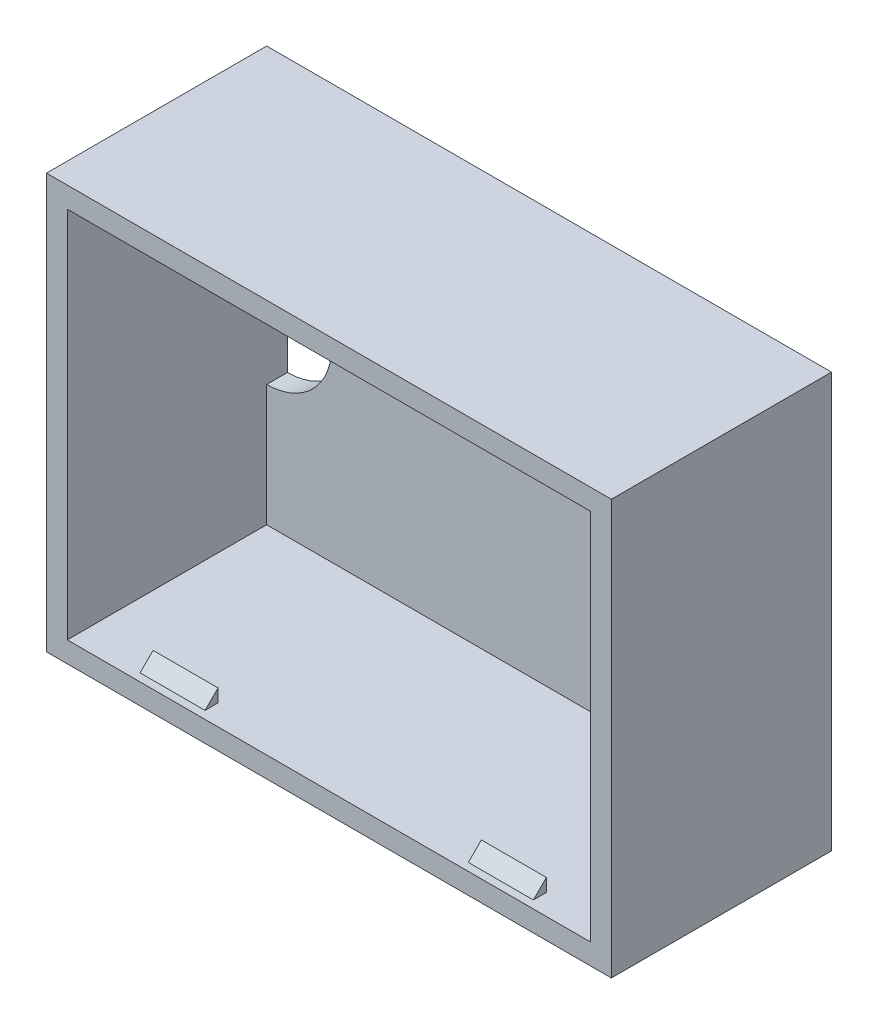
SolidWorks part; units mm, degrees
ref_plane "Front Plane" through (0, 0, 0) normal (1, 0, 0) x (0, 1, 0)
ref_plane "Top Plane" through (0, 0, 0) normal (0, 0, 1) x (0, 1, 0)
ref_plane "Right Plane" through (0, 0, 0) normal (0, 1, 0) x (-1, 0, 0)
sketch "Sketch2" plane through (0, 0, 0) normal (0, 0, 1) x (0, 1, 0)
  line L1 (-15.95, -21.73) -> (15.95, -21.73)
  line L2 (-15.95, -21.73) -> (-15.95, 21.73)
  line L3 (-15.95, 21.73) -> (15.95, 21.73)
  line L4 (15.95, -21.73) -> (15.95, 21.73)
  line L5 (-15.95, -21.73) -> (15.95, 21.73) construction
  line L6 (-15.95, 21.73) -> (15.95, -21.73) construction
  point P0 (0, 0)
  dimension "D1" = 43.46
  dimension "D2" = 31.9
extrude "Boss-Extrude1" add sketch "Sketch2" along normal blind 16.94
shell "Shell1" thickness 1.6 removed face at (0, 0, 16.94)
sketch "Sketch3" plane through (0, -14.35, 0) normal (0, 1, 0) x (-1, 0, 0)
  line L0 (20.13, 1.6) -> (-20.13, 1.6) construction
  line L1 (-15.13, 16.34) -> (-10.13, 16.34)
  line L2 (-15.13, 16.34) -> (-15.13, 15.34)
  line L3 (-15.13, 15.34) -> (-10.13, 15.34)
  line L4 (-10.13, 16.34) -> (-10.13, 15.34)
  line L5 (-20.13, 16.94) -> (-20.13, 1.6) construction
  line L6 (20.13, 16.94) -> (20.13, 1.6) construction
  line L7 (10.13, 16.34) -> (15.13, 16.34)
  line L8 (10.13, 16.34) -> (10.13, 15.34)
  line L9 (10.13, 15.34) -> (15.13, 15.34)
  line L10 (15.13, 16.34) -> (15.13, 15.34)
  dimension "D2" = 13.74
  dimension "D3" = 5
  dimension "D4" = 5
  dimension "D6" = 13.74
  dimension "D7" = 5
  dimension "D8" = 5
extrude "Boss-Extrude2" add sketch "Sketch3" along normal blind 1
sketch "Sketch4" plane through (0, 14.35, 0) normal (0, -1, 0) x (1, 0, 0)
  line L0 (-20.13, 16.94) -> (-20.13, 1.6) construction
  line L1 (-15.13, 16.34) -> (-10.13, 16.34)
  line L2 (-15.13, 16.34) -> (-15.13, 15.34)
  line L3 (-15.13, 15.34) -> (-10.13, 15.34)
  line L4 (-10.13, 16.34) -> (-10.13, 15.34)
  line L5 (10.13, 16.34) -> (15.13, 16.34)
  line L6 (10.13, 16.34) -> (10.13, 15.34)
  line L7 (10.13, 15.34) -> (15.13, 15.34)
  line L8 (15.13, 16.34) -> (15.13, 15.34)
  line L9 (20.13, 16.94) -> (20.13, 1.6) construction
  line L10 (20.13, 1.6) -> (-20.13, 1.6) construction
  dimension "D3" = 5
  dimension "D4" = 5
  dimension "D2" = 5
  dimension "D5" = 5
  dimension "D7" = 13.74
  dimension "D8" = 13.74
extrude "Boss-Extrude3" add sketch "Sketch4" along normal blind 1
chamfer "Chamfer1" distance 1 angle 45 4 edges at (-12.63, -13.35, 16.34) (12.63, -13.35, 16.34) (-12.63, 13.35, 16.34) (12.63, 13.35, 16.34)
sketch "Sketch5" plane through (0, 0, 1.6) normal (0, 0, 1) x (1, 0, 0)
  line L0 (20.13, 0) -> (-20.13, 0) construction
  line L1 (20.13, -14.35) -> (20.13, 14.35) construction
  line L2 (-20.13, 14.35) -> (-20.13, -14.35) construction
  line L4 (-20.13, 5) -> (-20.13, -5)
  arc A0 (-20.13, -5) -> (-20.13, 5) centre (-20.13, 0) ccw
  dimension "D1" = 5
extrude "Cut-Extrude1" cut sketch "Sketch5" against normal through all
equation "\"BoxW\"= 28.3 + 2 * 0.2 + 2 * 1.6"
equation "\"BoxH\"= 39.86 + 2 * 0.2 + 2 * 1.6"
equation "\"BoxD\" = 13.34 + 2 * 0.2 + 2 * 1.6"
equation "\"Wall\"= 1.6"
equation "\"Lip\"= 1"
equation "\"CableHole\"= 5"
equation "\"D1@Sketch2\"=\"BoxH\""
equation "\"D2@Sketch2\"=\"BoxW\""
equation "\"D1@Boss-Extrude1\"=\"BoxD\""
equation "\"D1@Shell1\"=\"Wall\""
equation "\"LipHeight\"= 13.34 + 2 * 0.2"
equation "\"D1@Sketch3\"=\"Lip\""
equation "\"D2@Sketch3\"=\"LipHeight\""
equation "\"D5@Sketch3\"=\"Lip\""
equation "\"D6@Sketch3\"=\"LipHeight\""
equation "\"D1@Boss-Extrude2\"=\"Lip\""
equation "\"D7@Sketch4\"=\"LipHeight\""
equation "\"D8@Sketch4\"=\"LipHeight\""
equation "\"D1@Sketch5\"=\"CableHole\""
